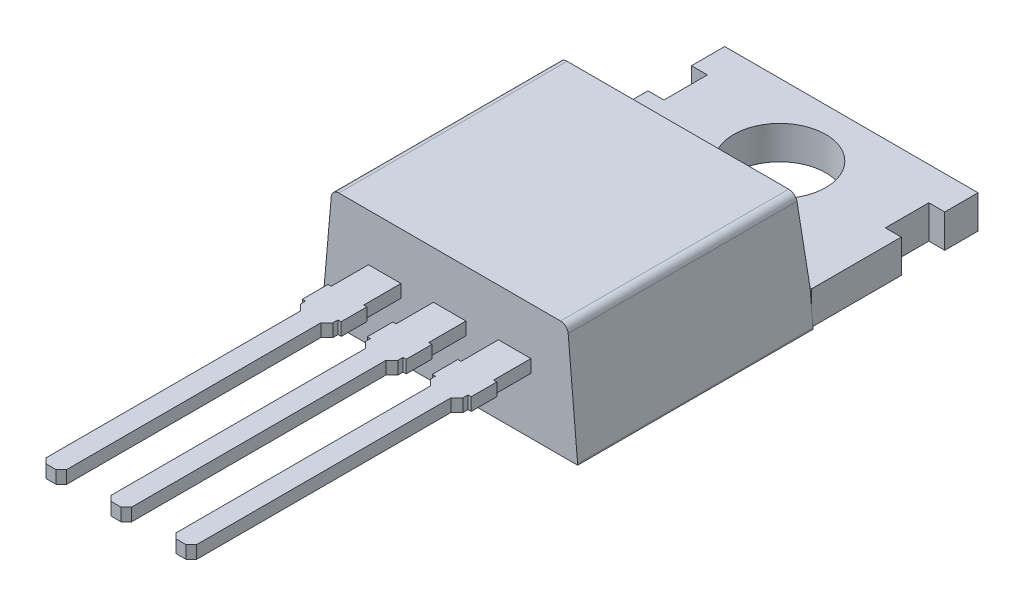
SolidWorks part; units mm, degrees
ref_plane "Front Plane" through (0, 0, 0) normal (0, 0, 1) x (1, 0, 0)
ref_plane "Top Plane" through (0, 0, 0) normal (0, 1, 0) x (1, 0, 0)
ref_plane "Right Plane" through (0, 0, 0) normal (1, 0, 0) x (0, 0, -1)
sketch "Sketch1" plane through (0, 0, 0) normal (0, 0, 1) x (1, 0, 0)
  line L0 (1.0311, 0) -> (-8.9689, 0)
  line L1 (-8.9689, 0) -> (-8.5752, 4.5)
  line L2 (-8.5752, 4.5) -> (0.6374, 4.5)
  line L4 (1.0311, 0) -> (0.6374, 4.5)
  dimension "D1" = 85
  dimension "D2" = 10
  dimension "D3" = 4.5
extrude "Boss-Extrude1" add sketch "Sketch1" along normal blind 9.2
fillet "Fillet1" radius 0.3 2 edges at (-8.5752, 4.5, 4.6) (0.6374, 4.5, 4.6)
ref_plane "Plane1" through (5, 0, 0) normal (1, 0, 0) x (0, 0, -1)
sketch "Sketch2" plane through (5, 0, 0) normal (1, 0, 0) x (0, 0, -1)
  line L0 (0, 4.5) -> (-0.28, 4.5)
  line L1 (-9.2, 4.5) -> (0, 4.5) construction
  line L2 (-0.28, 4.5) -> (0, 1.3)
  line L3 (0, 0) -> (0, 4.2261) construction
  line L4 (0, 1.3) -> (0, 4.5)
  line L5 (-9.2, 0) -> (0, 0) construction
  dimension "D1" = 1.3
  dimension "D2" = 5
extrude "Cut-Extrude1" cut sketch "Sketch2" against normal blind 19.2
sketch "Sketch3" plane through (0, 0, 0) normal (0, 0, -1) x (-1, 0, 0)
  line L0 (8.9689, 0) -> (-1.0311, 0) construction
  line L1 (8.9189, 0) -> (-0.9811, 0)
  line L2 (8.9189, 0) -> (8.9189, 1.3)
  line L3 (8.9189, 1.3) -> (-0.9811, 1.3)
  line L4 (-0.9811, 0) -> (-0.9811, 1.3)
  line L5 (8.8552, 1.3) -> (-0.9173, 1.3) construction
  point P4 (3.9689, 0)
  point P7 (3.9689, 0)
  dimension "D1" = 9.9
  dimension "D2" = 1.3
extrude "Boss-Extrude2" add sketch "Sketch3" along normal blind 6.5
sketch "Sketch4" plane through (0, 1.3, 0) normal (0, 1, 0) x (1, 0, 0)
  line L0 (-8.9189, 6.5) -> (-8.9189, 0) construction
  line L1 (-8.9189, 5.2) -> (-8.2971, 5.2)
  line L2 (-8.9189, 5.2) -> (-8.9189, 3.5)
  line L3 (-8.9189, 3.5) -> (-8.2971, 3.5)
  line L4 (-8.2971, 5.2) -> (-8.2971, 3.5)
  line L5 (-3.9689, 6.5) -> (-3.9689, 4.3685) construction
  line L6 (-8.9189, 6.5) -> (0.9811, 6.5) construction
  line L7 (0.9811, 5.2) -> (0.9811, 3.5)
  line L8 (0.9811, 3.5) -> (0.3592, 3.5)
  line L9 (0.3592, 5.2) -> (0.3592, 3.5)
  line L10 (0.9811, 5.2) -> (0.3592, 5.2)
  dimension "D1" = 1.7
  dimension "D2" = 1.3
extrude "Cut-Extrude3" cut sketch "Sketch4" against normal blind 16.5
sketch "Sketch5" plane through (0, 1.3, 0) normal (0, 1, 0) x (1, 0, 0)
  line L0 (-8.9189, 6.5) -> (0.9811, 6.5) construction
  circle A0 centre (-3.9689, 3.7) radius 1.8
  point P4 (-3.9689, 6.5)
  point P5 (0, 0)
  dimension "D1" = 3.6
  dimension "D2" = 2.8
extrude "Cut-Extrude4" cut sketch "Sketch5" against normal blind 16.5
sketch "Sketch8" plane through (0, 0, 9.2) normal (0, 0, 1) x (1, 0, 0)
  line L0 (-0.0243, 2.4) -> (-7.9136, 2.4) construction
  line L1 (-8.9689, 0) -> (1.0311, 0) construction
  line L2 (0.3625, 4.5) -> (-8.3003, 4.5) construction
  line L3 (-2.0639, 2.65) -> (-0.7939, 2.65)
  line L4 (-4.6039, 2.15) -> (-3.3339, 2.15)
  line L5 (-4.6039, 2.15) -> (-4.6039, 2.65)
  line L6 (-4.6039, 2.65) -> (-3.3339, 2.65)
  line L7 (-3.3339, 2.15) -> (-3.3339, 2.65)
  line L8 (-3.9689, 2.65) -> (-3.9689, 2.15) construction
  line L9 (-4.6039, 2.4) -> (-3.3339, 2.4) construction
  line L10 (-0.7939, 2.15) -> (-0.7939, 2.65)
  line L11 (-2.0639, 2.15) -> (-0.7939, 2.15)
  line L12 (-2.0639, 2.15) -> (-2.0639, 2.65)
  line L13 (-7.1439, 2.65) -> (-5.8739, 2.65)
  line L14 (-5.8739, 2.15) -> (-5.8739, 2.65)
  line L15 (-7.1439, 2.15) -> (-5.8739, 2.15)
  line L16 (-7.1439, 2.15) -> (-7.1439, 2.65)
  point P6 (-3.9689, 4.5)
  point P7 (-3.9689, 2.4)
  point P8 (-3.9689, 2.4)
  dimension "D1" = 2.4
  dimension "D2" = 1.27
  dimension "D3" = 0.5
  dimension "D4" = 2
  dimension "D5" = 2
extrude "Boss-Extrude4" add sketch "Sketch8" along normal blind 1.46
sketch "Sketch9" plane through (0, 0, 10.66) normal (0, 0, 1) x (1, 0, 0)
  line L0 (-3.3339, 2.65) -> (-4.6039, 2.65) construction
  line L1 (-4.7289, 2.65) -> (-3.2089, 2.65)
  line L2 (-4.7289, 2.65) -> (-4.7289, 2.15)
  line L3 (-4.7289, 2.15) -> (-3.2089, 2.15)
  line L4 (-3.2089, 2.65) -> (-3.2089, 2.15)
  line L5 (-3.9689, 2.15) -> (-3.9689, 2.65) construction
  line L6 (-4.7289, 2.4) -> (-3.2089, 2.4) construction
  line L7 (-2.1889, 2.65) -> (-0.6689, 2.65)
  line L8 (-0.6689, 2.65) -> (-0.6689, 2.15)
  line L9 (-2.1889, 2.15) -> (-0.6689, 2.15)
  line L10 (-2.1889, 2.65) -> (-2.1889, 2.15)
  line L11 (-7.2689, 2.65) -> (-5.7489, 2.65)
  line L12 (-5.7489, 2.65) -> (-5.7489, 2.15)
  line L13 (-7.2689, 2.15) -> (-5.7489, 2.15)
  line L14 (-7.2689, 2.65) -> (-7.2689, 2.15)
  point P0 (-3.9689, 2.4)
  point P7 (-3.9689, 2.65)
  dimension "D1" = 1.52
  dimension "D2" = 0.5
  dimension "D3" = 2
  dimension "D4" = 2
extrude "Boss-Extrude5" add sketch "Sketch9" along normal blind 1
sketch "Sketch10" plane through (0, 0, 11.66) normal (0, 0, 1) x (1, 0, 0)
  line L0 (-3.3339, 2.65) -> (-4.6039, 2.65) construction
  line L1 (-4.6039, 2.65) -> (-3.3339, 2.65)
  line L2 (-4.6039, 2.65) -> (-4.6039, 2.15)
  line L3 (-4.6039, 2.15) -> (-3.3339, 2.15)
  line L4 (-3.3339, 2.65) -> (-3.3339, 2.15)
  line L5 (-3.9689, 2.15) -> (-3.9689, 2.65) construction
  line L6 (-4.6039, 2.4) -> (-3.3339, 2.4) construction
  line L7 (-3.2089, 2.65) -> (-4.7289, 2.65) construction
  line L8 (-2.0639, 2.65) -> (-0.7939, 2.65)
  line L9 (-0.7939, 2.65) -> (-0.7939, 2.15)
  line L10 (-2.0639, 2.15) -> (-0.7939, 2.15)
  line L11 (-2.0639, 2.65) -> (-2.0639, 2.15)
  line L12 (-7.1439, 2.65) -> (-5.8739, 2.65)
  line L13 (-5.8739, 2.65) -> (-5.8739, 2.15)
  line L14 (-7.1439, 2.15) -> (-5.8739, 2.15)
  line L15 (-7.1439, 2.65) -> (-7.1439, 2.15)
  point P0 (-3.9689, 2.4)
  point P7 (-3.9689, 2.65)
  dimension "D1" = 0.5
  dimension "D2" = 1.27
  dimension "D3" = 2
  dimension "D4" = 2
extrude "Boss-Extrude6" add sketch "Sketch10" along normal blind 0.5
sketch "Sketch11" plane through (0, 0, 12.16) normal (0, 0, 1) x (1, 0, 0)
  line L0 (-3.3339, 2.65) -> (-4.6039, 2.65) construction
  line L1 (-4.3689, 2.65) -> (-3.5689, 2.65)
  line L2 (-4.3689, 2.65) -> (-4.3689, 2.15)
  line L3 (-4.3689, 2.15) -> (-3.5689, 2.15)
  line L4 (-3.5689, 2.65) -> (-3.5689, 2.15)
  line L5 (-3.9689, 2.15) -> (-3.9689, 2.65) construction
  line L6 (-4.3689, 2.4) -> (-3.5689, 2.4) construction
  line L7 (-1.8289, 2.65) -> (-1.0289, 2.65)
  line L8 (-1.0289, 2.65) -> (-1.0289, 2.15)
  line L9 (-1.8289, 2.15) -> (-1.0289, 2.15)
  line L10 (-1.8289, 2.65) -> (-1.8289, 2.15)
  line L11 (-6.9089, 2.65) -> (-6.1089, 2.65)
  line L12 (-6.1089, 2.65) -> (-6.1089, 2.15)
  line L13 (-6.9089, 2.15) -> (-6.1089, 2.15)
  line L14 (-6.9089, 2.65) -> (-6.9089, 2.15)
  line L15 (-5.8739, 2.65) -> (-7.1439, 2.65) construction
  point P0 (-3.9689, 2.4)
  point P8 (-3.9689, 2.65)
  dimension "D1" = 0.5
  dimension "D2" = 0.8
  dimension "D3" = 2
  dimension "D4" = 2
extrude "Boss-Extrude7" add sketch "Sketch11" along normal blind 10.08
chamfer "Chamfer1" distance 0.3 angle 45 6 edges at (-0.7939, 2.4, 12.16) (-2.0639, 2.4, 12.16) (-4.6039, 2.4, 12.16) (-3.3339, 2.4, 12.16) (-7.1439, 2.4, 12.16) (-5.8739, 2.4, 12.16)
chamfer "Chamfer2" distance 0.2 angle 45 6 edges at (-1.0289, 2.4, 22.24) (-1.8289, 2.4, 22.24) (-4.3689, 2.4, 22.24) (-3.5689, 2.4, 22.24) (-6.9089, 2.4, 22.24) (-6.1089, 2.4, 22.24)
sketch "Sketch15" plane through (0, 0, 0) normal (0, -1, 0) x (-1, 0, 0)
  line L0 (8.9689, 0) -> (7.9378, 0)
  line L1 (7.9378, 0) -> (7.9378, -8.2298)
  line L2 (7.9378, -8.2298) -> (0, -8.2298)
  line L3 (0, -8.2298) -> (0, 0)
  line L4 (0, 0) -> (-1.0311, 0)
  line L5 (-1.0311, 0) -> (-1.0311, -9.2)
  line L6 (-1.0311, -9.2) -> (8.9689, -9.2)
  line L7 (8.9689, -9.2) -> (8.9689, 0)
extrude "Boss-Extrude10" add sketch "Sketch15" along normal blind 0.05
